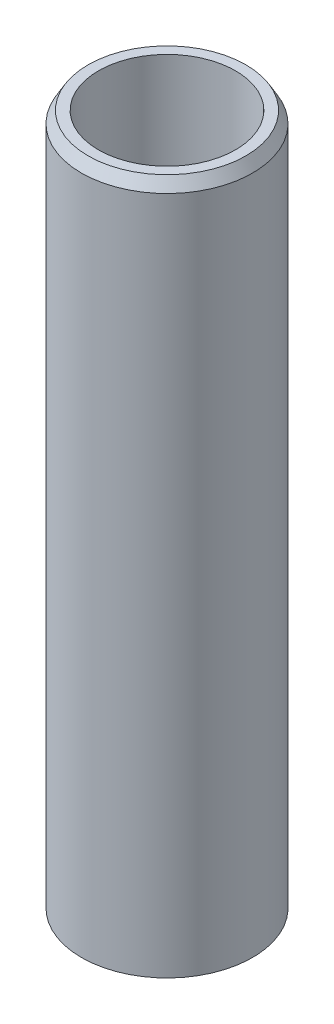
SolidWorks part; units mm, degrees
ref_plane "Front Plane" through (0, 0, 0) normal (0, 0, 1) x (1, 0, 0)
ref_plane "Top Plane" through (0, 0, 0) normal (0, 1, 0) x (1, 0, 0)
ref_plane "Right Plane" through (0, 0, 0) normal (1, 0, 0) x (0, 0, -1)
sketch "Sketch1" plane through (0, 0, 0) normal (0, 1, 0) x (1, 0, 0)
  circle A0 centre (0, 0) radius 27.5
  dimension "SHAFT_OD" = 55
extrude "Boss-Extrude1" add sketch "Sketch1" along normal blind 224.1488
sketch "Sketch2" plane through (0, 0, 0) normal (0, 1, 0) x (1, 0, 0)
  circle A0 centre (0, 0) radius 22.0198
  dimension "BORE_D" = 44.0397
extrude "Cut-Extrude1" cut sketch "Sketch2" along normal through all
chamfer "Chamfer1" distance 3.7158 angle 30 2 edges at (0, 224.1488, 27.5) (0, 0, 27.5) first distance on face at (0, 224.1488, 27.5) first distance on face at (0, 0, 22.0198)
